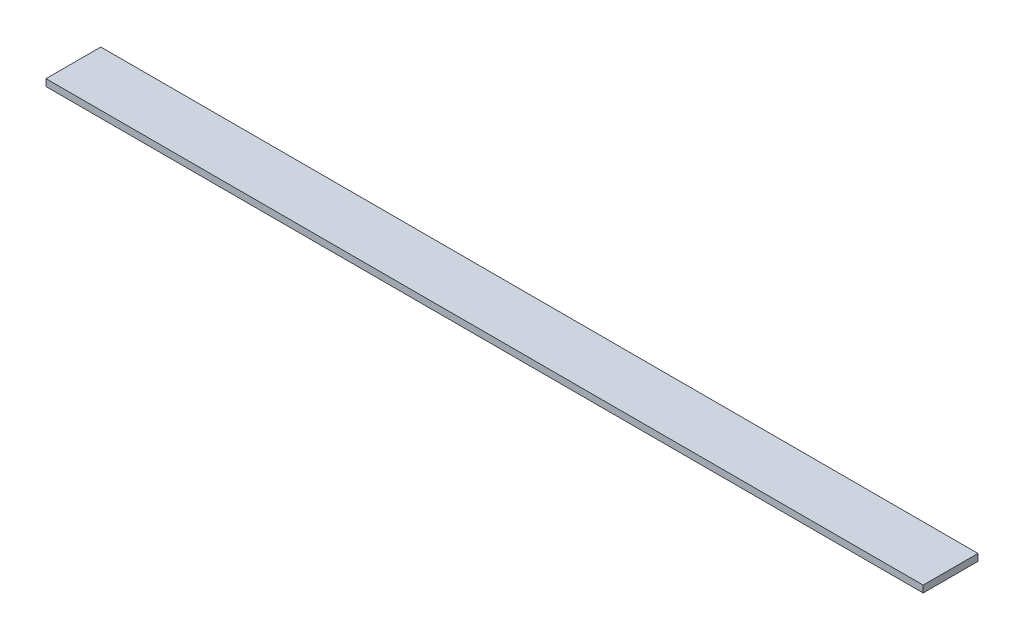
SolidWorks part; units mm, degrees
ref_plane "Front" through (0, 0, 0) normal (0, 0, 1) x (1, 0, 0)
ref_plane "Top" through (0, 0, 0) normal (0, 1, 0) x (1, 0, 0)
ref_plane "Right" through (0, 0, 0) normal (1, 0, 0) x (0, 0, -1)
sketch "Sketch1" plane through (0, 0, 0) normal (0, 1, 0) x (1, 0, 0)
  line L1 (-203.2, -12.7) -> (203.2, -12.7)
  line L2 (-203.2, -12.7) -> (-203.2, 12.7)
  line L3 (-203.2, 12.7) -> (203.2, 12.7)
  line L4 (203.2, -12.7) -> (203.2, 12.7)
  line L5 (-203.2, -12.7) -> (203.2, 12.7) construction
  line L6 (-203.2, 12.7) -> (203.2, -12.7) construction
  point P0 (0, 0)
  dimension "D1" = 406.4
  dimension "D2" = 25.4
base flange "Base-Flange1" sketch "Sketch1" thickness 3.175 reverse thickness direction no parameters "D1"=1.524
sketch "Bend-Lines1" plane through (0, 0, 0) normal (0, 1, 0) x (1, 0, 0)
sketch "Bounding-Box1" plane through (0, 0, 0) normal (0, 1, 0) x (1, 0, 0)
sheet metal parameters "Sheet-Metal8" thickness 3.175 parameters "D1"=1.524
flat pattern "Flat-Pattern8" [suppressed]
sketch "Bend-Lines2" plane through (0, 0, 0) normal (0, 1, 0) x (1, 0, 0)
sketch "Bounding-Box2" [suppressed] plane through (0, 0, 0) normal (0, 1, 0) x (1, 0, 0)
